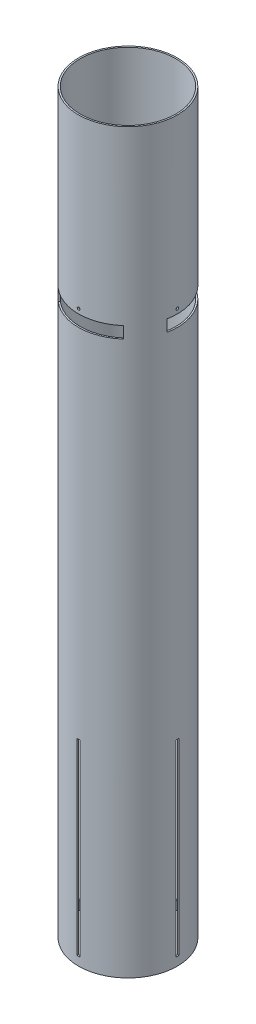
SolidWorks part; units mm, degrees
material "A-Glass Fiber"
ref_plane "Front Plane" through (0, 0, 0) normal (0, 0, 1) x (1, 0, 0)
ref_plane "Top Plane" through (0, 0, 0) normal (0, 1, 0) x (1, 0, 0)
ref_plane "Right Plane" through (0, 0, 0) normal (1, 0, 0) x (0, 0, -1)
sketch "Sketch1" plane through (0, 0, 0) normal (0, 1, 0) x (1, 0, 0)
  circle A0 centre (0, 0) radius 49.53
  circle A1 centre (0, 0) radius 51.1048
  dimension "D1" = 99.06
  dimension "D2" = 102.2096
extrude "Boss-Extrude1" add sketch "Sketch1" along normal blind 762
ref_plane "Plane1" through (0, 0, 0) normal (0.7071, 0, 0.7071) x (0.7071, 0, -0.7071)
ref_axis "Axis1" through (0, 762, 0) along (0, -1, 0)
sketch "Sketch2" plane through (0, 0, 0) normal (1, 0, 0) x (0, 0, -1)
  line L0 (0, 0) -> (0, 8.89)
  line L1 (1.5875, 8.89) -> (-1.5875, 8.89)
  line L2 (1.5875, 8.89) -> (1.5875, 203.2)
  line L3 (1.5875, 203.2) -> (-1.5875, 203.2)
  line L4 (-1.5875, 8.89) -> (-1.5875, 203.2)
  line L5 (1.5875, 8.89) -> (-1.5875, 203.2) construction
  line L6 (1.5875, 203.2) -> (-1.5875, 8.89) construction
  line L7 (51.1048, 762) -> (-51.1048, 762) construction
  line L8 (51.1048, 762) -> (-51.1048, 762)
  line L9 (0, 762) -> (0, 588.645)
  line L10 (-51.1048, 0) -> (51.1048, 0) construction
  circle A0 centre (0, 588.645) radius 1.3525
  point P0 (0, 106.045)
  dimension "D4" = 2.7051
  dimension "D1" = 3.175
  dimension "D2" = 194.31
  dimension "D5" = 588.645
  dimension "D3" = 203.2
extrude "Cut-Extrude1" cut sketch "Sketch2" against normal through all contours L4 L1 L2 L3 region at (0, 106.045, 0)
pattern_circular "CirPattern1" count 4 over 360 about axis through (0, 0, 0) along (0, 1, 0) of "Cut-Extrude1" reverse direction yes
extrude "Cut-Extrude2" cut sketch "Sketch2<3>" against normal through all contours A0 region at (0, 587.7157, 0.9293)
sketch "Sketch2<3>" plane through (0, 0, 0) normal (1, 0, 0) x (0, 0, -1) same geometry as "Sketch2"
pattern_circular "CirPattern2" count 4 over 360 about axis through (0, 762, 0) along (0, -1, 0) of "Cut-Extrude2"
sketch "Sketch3" plane through (0, 0, 0) normal (0.7071, 0, 0.7071) x (0.7071, 0, -0.7071)
  line L0 (0, 0) -> (0, 127) construction
  circle A0 centre (0, 127) radius 3.175
  dimension "D1" = 6.35
  dimension "D2" = 127
extrude "Cut-Extrude3" cut sketch "Sketch3" against normal through all
ref_plane "Plane3" through (0, 583.8825, 0) normal (0, 1, 0) x (1, 0, 0)
sketch "Sketch7" plane through (0, 583.8825, 0) normal (0, 1, 0) x (1, 0, 0)
  line L0 (0, 0) -> (-50.1228, -9.9701)
  line L1 (0, 0) -> (0, 93.232) construction
  line L2 (0, 0) -> (-16.4271, 48.3927)
  line L3 (-51.1048, 0) -> (0, 0) construction
  arc A0 (-51.0869, 1.3526) -> (-51.0869, -1.3525) centre (0, 0) ccw construction
  circle A1 centre (0, 0) radius 49.53 construction
  circle A2 centre (0, 0) radius 51.1048
  circle A3 centre (0, 0) radius 51.1048
  circle A4 centre (0, 0) radius 49.53
  circle A5 centre (0, 0) radius 51.1048 construction
  arc A6 (1.3526, 51.0869) -> (-1.3525, 51.0869) centre (0, 0) ccw construction
  arc A7 (-51.0869, 1.3526) -> (-51.0869, -1.3525) centre (0, 0) ccw
  arc A8 (1.3526, 51.0869) -> (-1.3525, 51.0869) centre (0, 0) ccw
  dimension "D1" = 82.5
  dimension "D3" = 11.25
  dimension "D2" = 0
extrude "Cut-Extrude4" cut sketch "Sketch7" against normal blind 12.065 contours A4 A3 L0 region at (-49.4835, 583.8825, 9.1481)
pattern_circular "CirPattern3" count 3 over 360 about axis through (0, 762, 0) along (0, -1, 0) of "Cut-Extrude4"
equation "\"D1@Boss-Extrude1\" = \"Aft_Section_Length\""
equation "\"AB_Coupler_OD_Length\"= 1in"
equation "\"AB_Coupling_Section_Length\"= 0.375in"
equation "\"AB_Coupler_Length\"= \"AB_Coupler_OD_Length\" + \"AB_Coupling_Section_Length\" * 2"
equation "\"AB_Coupler_Num_Screws\"= 4"
equation "\"AB_Coupling_Screw_Diameter\"= 0.1065in"
equation "\"Aft_Section_Length\" = 30in"
equation "\"D4@Sketch2\"=\"AB_Coupling_Screw_Diameter\""
equation "\"D1@CirPattern2\"=\"AB_Coupler_Num_Screws\""
equation "\"Rail_Nut_From_Bottom\"= 5in"
equation "\"Rail_Nut_Diam\"= 0.25in"
equation "\"D1@Sketch3\"=\"Rail_Nut_Diam\""
equation "\"D2@Sketch3\"=\"Rail_Nut_From_Bottom\""
equation "\"AB_BKHD_Thickness\" = 0.375in"
equation "\"AB_Mount_From_Bottom\" = 23.175in"
equation "\"Cutout_Angle\" = 60"
equation "\"Motor_OD\" = 54mm"
equation "\"Motor_Length\" = 401mm"
equation "\"Mid_Coupler_Length\" = 12in"
equation "\"AB_Paddle_Height\" = 0.375in"
equation "\"Num_Cutouts\" = 4"
equation "\"AB_Coupler_OD\"= 4.024in"
equation "\"AB_Coupler_ID\"= 3.7in"
equation "\"AB_Coupler_Surface_Diameter\"= 3.899in"
equation "\"AB_Central_Bushing_Length\" = 0.75in"
equation "\"Lead_Screw_Dist\" = 2in"
equation "\"Lead_Screw_Diam\" = 0.375in"
equation "\"Lead_Screw_Length\" = \"Mid_Coupler_Length\" + 2*0.375in + 2*0.5in"
equation "\"Paddle_Pin_Offset\" = 0.25in"
equation "\"Paddle_Pin_Radius\" = 2.25*2/3in"
equation "\"Paddle_Gear_OD\" = 3.2in"
equation "\"Fwd_BKHD_From_Top\" = 18in"
equation "\"Body_Tube_OD\"= 4.024in"
equation "\"Body_Tube_ID\"= 3.90in"
equation "\"Coupler_OD\" = 3.899in"
equation "\"Coupler_ID\" = 3.755in"
equation "\"Fwd_Section_Length\" = 25in"
equation "\"Mid_Section_Length\" = 6in"
equation "\"Aft_Upper_Tube_Length\" = 10in"
equation "\"Aft_Lower_Tube_Length\" = 18in"
equation "\"Nosecone_Coupler_Length\" = 5in"
equation "\"Avionics_Bulkhead_Thickness\" = 0.25in"
equation "\"Avionics_Bulkhead_Lip\" = 0.125in"
equation "\"Avionics_Board_Length\" = \"Mid_Coupler_Length\" - 2*\"Avionics_Bulkhead_Lip\""
equation "\"Lead_Screw_Hole_Diam\" = (27/64)*1in"
equation "\"Centering_Ring_Cutout_Dia\"=1.5in"
equation "\"D2@Sketch1\"=\"Body_Tube_OD\""
equation "\"D1@Sketch1\"=\"Body_Tube_ID\""
